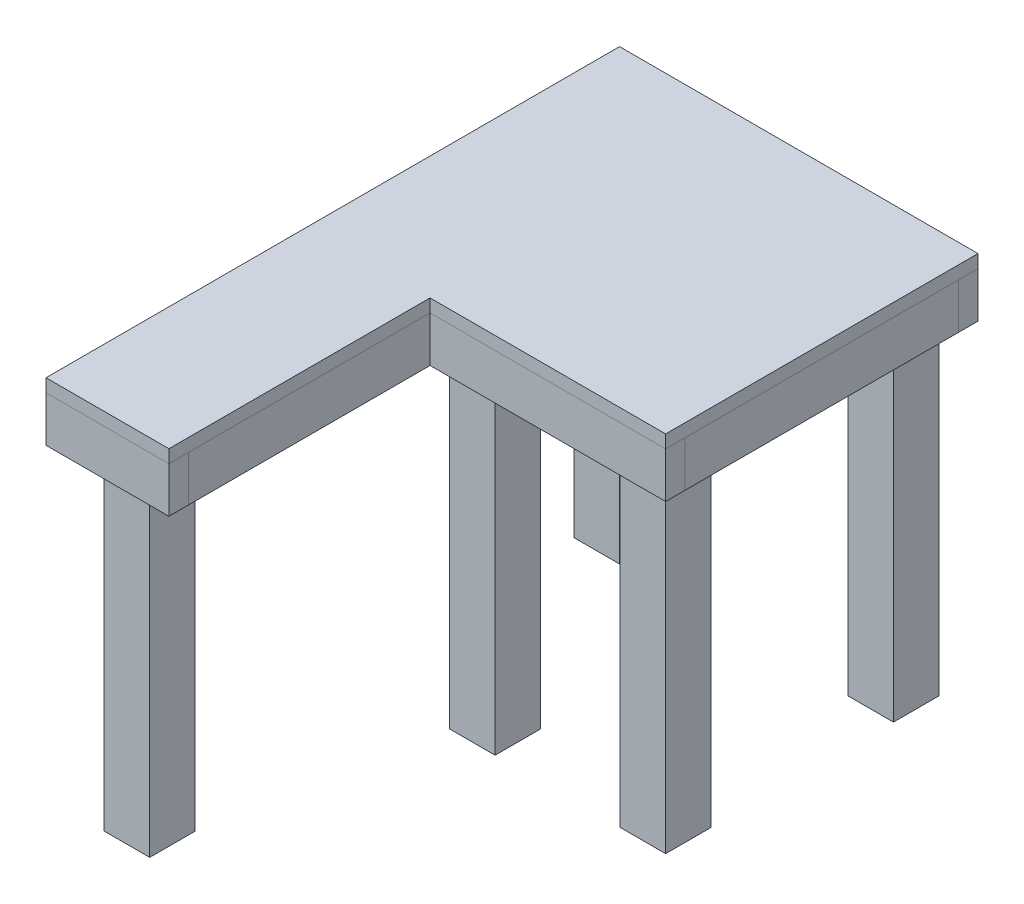
SolidWorks part; units mm, degrees
note: The reader was unsure of these and kept them because the rebuilt part matched: shared geometry of "Sketch1<3>", "Sketch1<4>", "Sketch1<5>", "Sketch1<6>", "Sketch1<7>", "Sketch1<8>", "Sketch1<9>".
ref_plane "Front Plane" through (0, 0, 0) normal (0, 0, 1) x (1, 0, 0)
ref_plane "Top Plane" through (0, 0, 0) normal (0, 1, 0) x (1, 0, 0)
ref_plane "Right Plane" through (0, 0, 0) normal (1, 0, 0) x (0, 0, -1)
sketch "Sketch1" plane through (0, 0, 0) normal (0, 1, 0) x (1, 0, 0)
  line L0 (-700, -510) -> (-460, -510)
  line L1 (-460, -510) -> (-460, 0)
  line L2 (-460, 0) -> (0, 0)
  line L3 (0, 0) -> (0, 610)
  line L4 (0, 610) -> (-700, 610)
  line L5 (-700, 610) -> (-700, -510)
  line L6 (0, 38.1) -> (-498.1, 38.1)
  line L7 (-661.9, 571.9) -> (-573, 571.9)
  line L8 (-661.9, 571.9) -> (-661.9, 483)
  line L9 (-661.9, 483) -> (-573, 483)
  line L10 (-573, 571.9) -> (-573, 483)
  line L11 (-624.45, -383) -> (-535.55, -383)
  line L12 (-624.45, -383) -> (-624.45, -471.9)
  line L13 (-624.45, -471.9) -> (-535.55, -471.9)
  line L14 (-535.55, -383) -> (-535.55, -471.9)
  line L15 (-127, 571.9) -> (-38.1, 571.9)
  line L16 (-127, 571.9) -> (-127, 483)
  line L17 (-127, 483) -> (-38.1, 483)
  line L18 (-38.1, 571.9) -> (-38.1, 483)
  line L19 (-127, 127) -> (-38.1, 127)
  line L20 (-127, 127) -> (-127, 38.1)
  line L21 (-127, 38.1) -> (-38.1, 38.1)
  line L22 (-38.1, 127) -> (-38.1, 38.1)
  line L23 (-460, 127) -> (-371.1, 127)
  line L24 (-460, 127) -> (-460, 38.1)
  line L25 (-460, 38.1) -> (-371.1, 38.1)
  line L26 (-371.1, 127) -> (-371.1, 38.1)
  line L27 (-498.1, 38.1) -> (-498.1, -471.9)
  line L28 (-460, -471.9) -> (-700, -471.9)
  line L29 (-661.9, -471.9) -> (-661.9, 610)
  line L30 (-661.9, 571.9) -> (0, 571.9)
  line L31 (-38.1, 571.9) -> (-38.1, 38.1)
  line L32 (-460, 38.1) -> (-460, 0)
  point P19 (-580, -471.9)
  point P20 (-580, -510)
  dimension "D1" = 240
  dimension "D2" = 610
  dimension "D3" = 700
  dimension "D4" = 1120
  dimension "D5" = 88.9
  dimension "D6" = 88.9
  dimension "D7" = 88.9
  dimension "D8" = 38.1
  dimension "D9" = 38.1
  dimension "D10" = 38.1
  dimension "D11" = 38.1
  dimension "D12" = 38.1
  dimension "D13" = 88.9
  dimension "D14" = 38.1
  dimension "D15" = 38.1
  dimension "D16" = 88.9
  dimension "D17" = 88.9
  dimension "D18" = 38.1
  dimension "D19" = 38.1
extrude "Boss-Extrude1" add sketch "Sketch1" along normal blind 25.4 contours L0 L1 L2 L3 L4 L5
extrude "Boss-Extrude2" add sketch "Sketch1<3>" against normal offset from surface (722.6 mm away) 748 separate body contours L14 L11 L12 L13 | L26 L23 L24 L25 | L22 L19 L20 L21 | L18 L15 L16 L17 | L10 L7 L8 L9 up to face at (-386.6667, 25.4, -33.3333)
sketch "Sketch1<3>" plane through (0, 0, 0) normal (0, 1, 0) x (1, 0, 0) same geometry as "Sketch1"
extrude "Boss-Extrude3" add sketch "Sketch1<4>" against normal blind 88.9 separate body contours L28 L1 L2 L3 L6 L27
sketch "Sketch1<4>" plane through (0, 0, 0) normal (0, 1, 0) x (1, 0, 0) same geometry as "Sketch1"
extrude "Boss-Extrude4" add sketch "Sketch1<5>" against normal blind 88.9 separate body contours L32 L6 L27 L28 L1
sketch "Sketch1<5>" plane through (0, 0, 0) normal (0, 1, 0) x (1, 0, 0) same geometry as "Sketch1"
extrude "Boss-Extrude6" add sketch "Sketch1<6>" against normal blind 88.9 separate body contours L1 L28 L13 L5 L0
sketch "Sketch1<6>" plane through (0, 0, 0) normal (0, 1, 0) x (1, 0, 0) same geometry as "Sketch1"
extrude "Boss-Extrude7" add sketch "Sketch1<7>" against normal blind 88.9 separate body contours L28 L29 L8 L4 L5
sketch "Sketch1<7>" plane through (0, 0, 0) normal (0, 1, 0) x (1, 0, 0) same geometry as "Sketch1"
extrude "Boss-Extrude8" add sketch "Sketch1<8>" against normal blind 88.9 separate body contours L7 L30 L15 L3 L4 L29
sketch "Sketch1<8>" plane through (0, 0, 0) normal (0, 1, 0) x (1, 0, 0) same geometry as "Sketch1"
extrude "Boss-Extrude9" add sketch "Sketch1<9>" against normal blind 88.9 separate body contours L18 L31 L22 L6 L3 L30
sketch "Sketch1<9>" plane through (0, 0, 0) normal (0, 1, 0) x (1, 0, 0) same geometry as "Sketch1"
